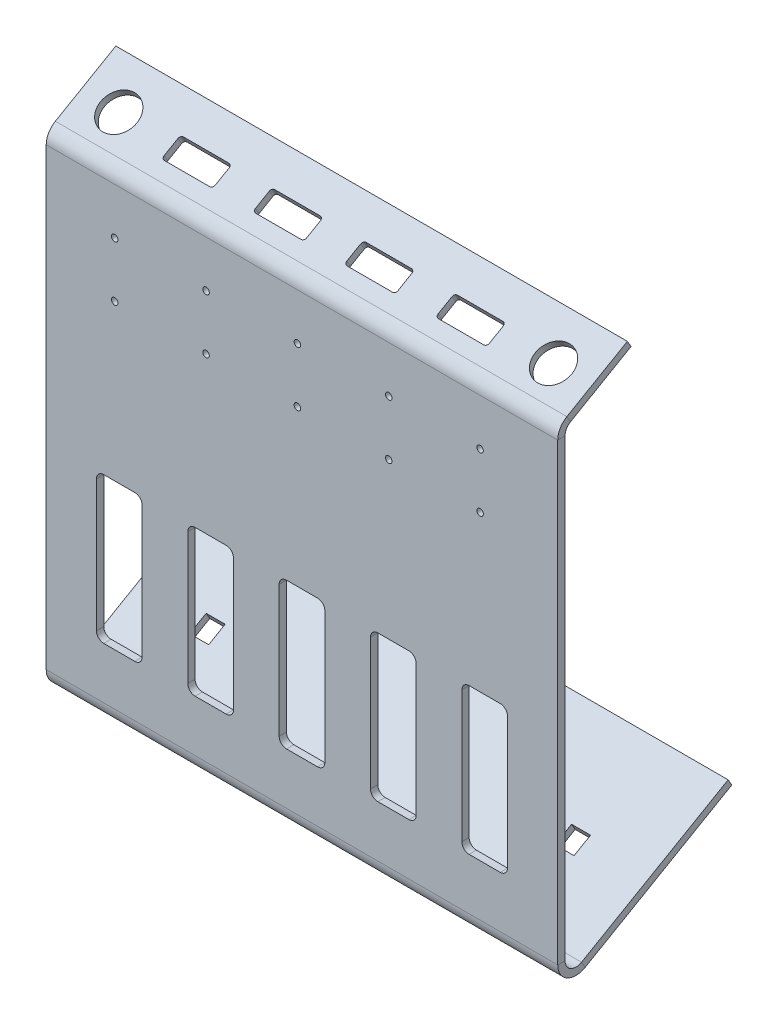
SolidWorks part; units mm, degrees
note: The reader was unsure of these and kept them because the rebuilt part matched: flange length of "Edge-Flange1", "Edge-Flange2".
ref_plane "Front Plane" through (0, 0, 0) normal (0, 0, 1) x (1, 0, 0)
ref_plane "Top Plane" through (0, 0, 0) normal (0, 1, 0) x (1, 0, 0)
ref_plane "Right Plane" through (0, 0, 0) normal (1, 0, 0) x (0, 0, -1)
sketch "Sketch1" plane through (0, 0, 0) normal (0, 0, 1) x (1, 0, 0)
  line L1 (0, 0) -> (177.8, 0)
  line L2 (0, 0) -> (0, 157.988)
  line L3 (0, 157.988) -> (177.8, 157.988)
  line L4 (177.8, 0) -> (177.8, 157.988)
  dimension "D1" = 157.988
  dimension "D2" = 177.8
base flange "Base-Flange1" sketch "Sketch1" thickness 2.54 reverse thickness direction no parameters "D1"=0.7366
sketch "Sketch6" plane through (0, 0, 0) normal (0, 0, 1) x (1, 0, 0)
  line L0 (0, 0) -> (177.8, 0) construction
  line L1 (20.0025, 17.8918) -> (30.7975, 17.8918)
  line L2 (17.4625, 20.4318) -> (17.4625, 66.1518)
  line L3 (20.0025, 68.6918) -> (30.7975, 68.6918)
  line L4 (33.3375, 20.4318) -> (33.3375, 66.1518)
  line L5 (0, 157.988) -> (0, 0) construction
  arc A0 (33.3375, 20.4318) -> (30.7975, 17.8918) centre (30.7975, 20.4318) cw
  arc A1 (20.0025, 17.8918) -> (17.4625, 20.4318) centre (20.0025, 20.4318) cw
  arc A2 (30.7975, 68.6918) -> (33.3375, 66.1518) centre (30.7975, 66.1518) cw
  arc A3 (17.4625, 66.1518) -> (20.0025, 68.6918) centre (20.0025, 66.1518) cw
  dimension "D5" = 2.54
  dimension "D1" = 50.8
  dimension "D2" = 15.875
  dimension "D3" = 17.8918
  dimension "D4" = 17.4625
extrude "Cut-Extrude1" cut sketch "Sketch6" against normal through all normal cut yes
hole_wizard "#4-40 Tapped Hole1" positions "3DSketch1" profile "Sketch26" tap size "#4-40" standard "ANSI Inch" end condition up to next
sketch3d "3DSketch1"
  line L0 (23.8125, 122.7745, 0) -> (23.8125, 141.8245, 0) construction
  line L4 (0, 157.988, 0) -> (0, 0, 0) construction
  line L5 (177.8, 157.988, 0) -> (0, 157.988, 0) construction
  point P0 (23.8125, 141.8245, 0)
  point P2 (23.8125, 122.7745, 0)
  dimension "D2" = 19.05
  dimension "D1" = 23.8125
  dimension "D3" = 16.1635
cosmetic thread "Hole Thread1"
cosmetic thread "Hole Thread2"
sketch "Sketch26" plane through (23.8125, 141.8245, 0) normal (1, 0, 0) x (0, -1, 0)
  line L0 (0, 0) -> (0, 2.54)
  line L1 (0, 2.54) -> (1.1303, 2.54)
  line L2 (1.1303, 2.54) -> (1.1303, 0)
  line L5 (1.1303, 0) -> (0, 0)
  line L11 (0, -6.35) -> (0, 107.95) construction
  dimension "Thru Tap Drill Dia." = 2.2606
  dimension "Thru Tap Drill Depth" = 2.54
pattern_linear "LPattern1" count 5 spacing 31.75 along (1, 0, 0) of "Cut-Extrude1", "#4-40 Tapped Hole1"
cosmetic thread "Hole Thread3"
cosmetic thread "Hole Thread4"
cosmetic thread "Hole Thread5"
cosmetic thread "Hole Thread6"
cosmetic thread "Hole Thread7"
cosmetic thread "Hole Thread8"
cosmetic thread "Hole Thread9"
cosmetic thread "Hole Thread10"
edge flange "Edge-Flange1" sketch "Sketch20" flange angle 120 flange length 27.94 flange position bend outside bend radius 3.81 thickness 2.54 relief rectangular parameters "D6"=10
sketch "Sketch20" plane through (0, 157.988, -2.54) normal (0, 0.866, 0.5) x (1, 0, 0)
  line L2 (0, 0) -> (0, 26.4735)
  line L3 (0, 26.4735) -> (177.8, 26.4735)
  line L4 (177.8, 26.4735) -> (177.8, 0)
  line L7 (177.8, 0) -> (0, 0) construction
  line L8 (177.8, 0) -> (0, 0)
bend "EdgeBend1" bend radius 3.81 bend angle 60 parameters "D5"=1
edge flange "Edge-Flange2" sketch "Sketch23" flange angle 60 flange length 69.85 flange position bend outside bend radius 3.81 thickness 2.54 relief rectangular parameters "D6"=10
sketch "Sketch23" plane through (0, 0, -2.54) normal (0, 0.866, 0.5) x (1, 0, 0)
  line L2 (0, 0) -> (0, 65.4506)
  line L3 (0, 65.4506) -> (177.8, 65.4506)
  line L4 (177.8, 65.4506) -> (177.8, 0)
  line L9 (177.8, 0) -> (0, 0) construction
  line L10 (177.8, 0) -> (0, 0)
bend "EdgeBend2" bend radius 3.81 bend angle 120 parameters "D5"=2
sketch "Sketch25" plane through (0, 121.2406, 69.9983) normal (0, 0.866, 0.5) x (1, 0, 0)
  line L0 (177.8, 108.7671) -> (0, 108.7671) construction
  line L1 (33.401, 97.3371) -> (49.149, 97.3371)
  line L2 (32.385, 96.3211) -> (32.385, 90.7331)
  line L3 (33.401, 89.7171) -> (49.149, 89.7171)
  line L4 (50.165, 96.3211) -> (50.165, 90.7331)
  line L5 (0, 108.7671) -> (0, 84.4933) construction
  arc A0 (50.165, 96.3211) -> (49.149, 97.3371) centre (49.149, 96.3211) ccw
  arc A1 (49.149, 89.7171) -> (50.165, 90.7331) centre (49.149, 90.7331) ccw
  arc A2 (33.401, 89.7171) -> (32.385, 90.7331) centre (33.401, 90.7331) cw
  arc A3 (32.385, 96.3211) -> (33.401, 97.3371) centre (33.401, 96.3211) cw
  dimension "D5" = 1.016
  dimension "D1" = 7.62
  dimension "D2" = 17.78
  dimension "D3" = 11.43
  dimension "D4" = 32.385
extrude "Cut-Extrude4" cut sketch "Sketch25" against normal up to next
pattern_linear "LPattern2" count 4 spacing 31.75 along (1, 0, 0) of "Cut-Extrude4"
sketch "Sketch28" plane through (0, -8.2489, -4.7625) normal (0, -0.866, -0.5) x (1, 0, 0)
  line L0 (28.702, -31.3307) -> (149.098, -31.3307) construction
  line L1 (22.098, -28.0287) -> (28.702, -28.0287)
  line L2 (22.098, -28.0287) -> (22.098, -34.6327)
  line L3 (22.098, -34.6327) -> (28.702, -34.6327)
  line L4 (28.702, -28.0287) -> (28.702, -34.6327)
  line L5 (149.098, -28.0287) -> (155.702, -28.0287)
  line L6 (149.098, -28.0287) -> (149.098, -34.6327)
  line L7 (149.098, -34.6327) -> (155.702, -34.6327)
  line L8 (155.702, -28.0287) -> (155.702, -34.6327)
  line L9 (88.9, -64.3507) -> (88.9, -31.3307) construction
  line L10 (177.8, -64.3507) -> (0, -64.3507) construction
  point P8 (28.702, -31.3307)
  dimension "D1" = 6.604
  dimension "D2" = 127
  dimension "D3" = 33.02
extrude "Cut-Extrude5" cut sketch "Sketch28" against normal up to next
sketch "Sketch24" plane through (0, 121.2406, 69.9983) normal (0, 0.866, 0.5) x (1, 0, 0)
  line L0 (0, 108.7671) -> (0, 84.4933) construction
  line L1 (177.8, 84.4933) -> (177.8, 108.7671) construction
  line L2 (177.8, 108.7671) -> (0, 108.7671) construction
  circle A0 centre (13.335, 94.5431) radius 6.35
  circle A1 centre (164.465, 94.5431) radius 6.35
  dimension "D2" = 12.7
  dimension "D1" = 13.335
  dimension "D3" = 13.335
  dimension "D4" = 14.224
extrude "Cut-Extrude3" cut sketch "Sketch24" against normal up to next
sketch "Sketch7" plane through (0, 0, 0) normal (0, 0, 1) x (1, 0, 0)
  line L0 (50.8, 5.1918) -> (127, 5.1918) construction
  line L2 (88.9, 17.8918) -> (88.9, 5.1918) construction
  line L4 (51.7525, 17.8918) -> (62.5475, 17.8918) construction
  line L5 (83.5025, 17.8918) -> (94.2975, 17.8918) construction
  text T0 "Your Text Here" font "Century Gothic" height 6.35
  dimension "D1" = 12.7
  dimension "D2" = 76.2
sketch "Bend-Lines1" plane through (0, 0, 0) normal (0, 1, 0) x (1, 0, 0)
sketch "Bounding-Box1" plane through (0, 0, 0) normal (0, 1, 0) x (1, 0, 0)
sheet metal parameters "Sheet-Metal1" thickness 2.54 parameters "D1"=0.7366
flat pattern "Flat-Pattern1"
sketch "Bend-Lines2" plane through (0, 0, 0) normal (0, 1, 0) x (1, 0, 0)
sketch3d "Bounding-Box2"
  line L0 (0, 0, 0) -> (177.8, 0, 0) construction
  line L1 (0, 157.988, 0) -> (177.8, 157.988, 0) construction
  line L2 (0, 0, 0) -> (0, 157.988, 0) construction
  line L3 (177.8, 0, 0) -> (177.8, 157.988, 0) construction
sheet metal parameters "Sheet-Metal2" thickness 2.54 parameters "D1"=0.7366
flat pattern "Flat-Pattern1"
sketch "Bend-Lines2" plane through (0, 0, 0) normal (0, 1, 0) x (1, 0, 0)
sketch3d "Bounding-Box2"
  line L0 (0, 0, 0) -> (177.8, 0, 0) construction
  line L1 (0, 157.988, 0) -> (177.8, 157.988, 0) construction
  line L2 (0, 0, 0) -> (0, 157.988, 0) construction
  line L3 (177.8, 0, 0) -> (177.8, 157.988, 0) construction
sheet metal parameters "Sheet-Metal3" thickness 2.54 parameters "D1"=0.7366
flat pattern "Flat-Pattern1"
sketch "Bend-Lines2" plane through (0, 0, 0) normal (0, 1, 0) x (1, 0, 0)
sketch3d "Bounding-Box2"
  line L0 (0, 0, 0) -> (177.8, 0, 0) construction
  line L1 (0, 157.988, 0) -> (177.8, 157.988, 0) construction
  line L2 (0, 0, 0) -> (0, 157.988, 0) construction
  line L3 (177.8, 0, 0) -> (177.8, 157.988, 0) construction
sheet metal parameters "Sheet-Metal9" thickness 2.54 parameters "D1"=0.7366
flat pattern "Flat-Pattern1"
sketch "Bend-Lines2" plane through (0, 0, 0) normal (0, 0, 1) x (1, 0, 0)
  line L0 (177.8, 160.6479) -> (0, 160.6479) construction
  line L1 (177.8, 160.6479) -> (0, 160.6479) construction
sketch3d "Bounding-Box2"
  line L0 (177.8, 187.5816, 0) -> (177.8, 0, 0) construction
  line L1 (0, 187.5816, 0) -> (0, 0, 0) construction
  line L2 (177.8, 187.5816, 0) -> (0, 187.5816, 0) construction
  line L3 (177.8, 0, 0) -> (0, 0, 0) construction
bend of the flat pattern "Flatten-<EdgeBend1>1"
sheet metal parameters "Sheet-Metal10" thickness 2.54 parameters "D1"=0.7366
flat pattern "Flat-Pattern1"
sketch "Bend-Lines2" plane through (0, 0, 0) normal (0, 0, 1) x (1, 0, 0)
  line L0 (177.8, 160.6479) -> (0, 160.6479) construction
  line L1 (177.8, 160.6479) -> (0, 160.6479) construction
  line L2 (0, -5.3198) -> (177.8, -5.3198) construction
  line L3 (0, -5.3198) -> (177.8, -5.3198) construction
sketch3d "Bounding-Box2"
  line L0 (177.8, 187.5816, 0) -> (177.8, -69.491, 0) construction
  line L1 (0, 187.5816, 0) -> (0, -69.491, 0) construction
  line L2 (177.8, 187.5816, 0) -> (0, 187.5816, 0) construction
  line L3 (177.8, -69.491, 0) -> (0, -69.491, 0) construction
bend of the flat pattern "Flatten-<EdgeBend1>1"
bend of the flat pattern "Flatten-<EdgeBend2>1"
sheet metal parameters "Sheet-Metal11" thickness 2.54 parameters "D1"=0.7366
flat pattern "Flat-Pattern1"
sketch "Bend-Lines2" plane through (0, 0, 0) normal (0, 0, 1) x (1, 0, 0)
  line L0 (177.8, 160.6479) -> (0, 160.6479) construction
  line L1 (177.8, 160.6479) -> (0, 160.6479) construction
  line L2 (0, -5.3198) -> (177.8, -5.3198) construction
  line L3 (0, -5.3198) -> (177.8, -5.3198) construction
sketch3d "Bounding-Box2"
  line L0 (177.8, 187.5816, 0) -> (177.8, -69.491, 0) construction
  line L1 (0, 187.5816, 0) -> (0, -69.491, 0) construction
  line L2 (177.8, 187.5816, 0) -> (0, 187.5816, 0) construction
  line L3 (177.8, -69.491, 0) -> (0, -69.491, 0) construction
bend of the flat pattern "Flatten-<EdgeBend1>1"
bend of the flat pattern "Flatten-<EdgeBend2>1"
sheet metal parameters "Sheet-Metal12" thickness 2.54 parameters "D1"=0.7366
flat pattern "Flat-Pattern1"
sketch "Bend-Lines2" plane through (0, 0, 0) normal (0, 0, 1) x (1, 0, 0)
  line L0 (177.8, 161.0912) -> (0, 161.0912) construction
  line L1 (177.8, 161.0912) -> (0, 161.0912) construction
  line L2 (0, -4.8764) -> (177.8, -4.8764) construction
  line L3 (0, -4.8764) -> (177.8, -4.8764) construction
sketch3d "Bounding-Box2"
  line L0 (177.8, 187.6881, 0) -> (177.8, -69.2642, 0) construction
  line L1 (0, 187.6881, 0) -> (0, -69.2642, 0) construction
  line L2 (177.8, 187.6881, 0) -> (0, 187.6881, 0) construction
  line L3 (177.8, -69.2642, 0) -> (0, -69.2642, 0) construction
bend of the flat pattern "Flatten-<EdgeBend1>1"
bend of the flat pattern "Flatten-<EdgeBend2>1"
sheet metal parameters "Sheet-Metal13" thickness 2.54 parameters "D1"=0.7366
flat pattern "Flat-Pattern1"
sketch "Bend-Lines2" plane through (0, 0, 0) normal (0, 0, 1) x (1, 0, 0)
  line L0 (177.8, 160.6479) -> (0, 160.6479) construction
  line L1 (177.8, 160.6479) -> (0, 160.6479) construction
  line L2 (0, -5.3198) -> (177.8, -5.3198) construction
  line L3 (0, -5.3198) -> (177.8, -5.3198) construction
sketch3d "Bounding-Box2"
  line L0 (177.8, 187.5816, 0) -> (177.8, -69.491, 0) construction
  line L1 (0, 187.5816, 0) -> (0, -69.491, 0) construction
  line L2 (177.8, 187.5816, 0) -> (0, 187.5816, 0) construction
  line L3 (177.8, -69.491, 0) -> (0, -69.491, 0) construction
bend of the flat pattern "Flatten-<EdgeBend1>1"
bend of the flat pattern "Flatten-<EdgeBend2>1"
sheet metal parameters "Sheet-Metal14" thickness 2.54 parameters "D1"=0.7366
flat pattern "Flat-Pattern1"
sketch "Bend-Lines2" plane through (0, 0, 0) normal (0, 0, 1) x (1, 0, 0)
  line L0 (177.8, 161.0912) -> (0, 161.0912) construction
  line L1 (177.8, 161.0912) -> (0, 161.0912) construction
  line L2 (0, -4.8764) -> (177.8, -4.8764) construction
  line L3 (0, -4.8764) -> (177.8, -4.8764) construction
sketch3d "Bounding-Box2"
  line L0 (177.8, 187.6881, 0) -> (177.8, -69.2642, 0) construction
  line L1 (0, 187.6881, 0) -> (0, -69.2642, 0) construction
  line L2 (177.8, 187.6881, 0) -> (0, 187.6881, 0) construction
  line L3 (177.8, -69.2642, 0) -> (0, -69.2642, 0) construction
sheet metal parameters "Sheet-Metal15" thickness 2.54 parameters "D1"=0.7366
flat pattern "Flat-Pattern1"
sketch "Bend-Lines2" plane through (0, 0, 0) normal (0, 0, 1) x (1, 0, 0)
  line L0 (177.8, 160.6479) -> (0, 160.6479) construction
  line L1 (177.8, 160.6479) -> (0, 160.6479) construction
  line L2 (0, -5.3198) -> (177.8, -5.3198) construction
  line L3 (0, -5.3198) -> (177.8, -5.3198) construction
sketch3d "Bounding-Box2"
  line L0 (177.8, 187.5816, 0) -> (177.8, -69.491, 0) construction
  line L1 (0, 187.5816, 0) -> (0, -69.491, 0) construction
  line L2 (177.8, 187.5816, 0) -> (0, 187.5816, 0) construction
  line L3 (177.8, -69.491, 0) -> (0, -69.491, 0) construction
bend of the flat pattern "Flatten-<EdgeBend1>1"
bend of the flat pattern "Flatten-<EdgeBend2>1"
equation "\"D3@Sketch24\"=\"D1@Sketch24\""
